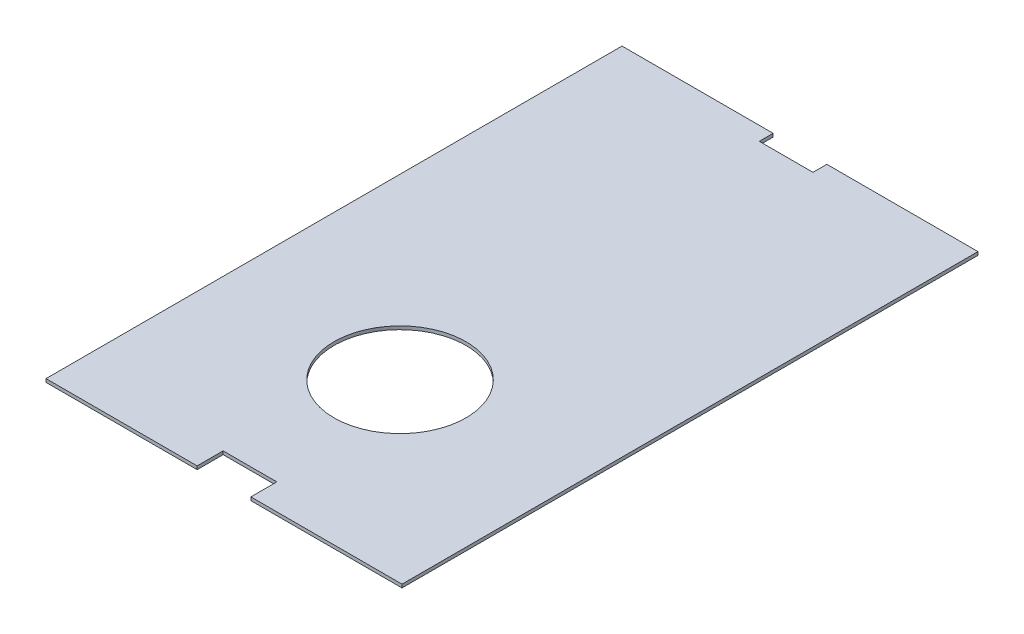
SolidWorks part; units mm, degrees
ref_plane "Front Plane" through (0, 0, 0) normal (0, 0, 1) x (1, 0, 0)
ref_plane "Top Plane" through (0, 0, 0) normal (0, 1, 0) x (1, 0, 0)
ref_plane "Right Plane" through (0, 0, 0) normal (1, 0, 0) x (0, 0, -1)
sketch "BaseSketch" plane through (0, 0, 0) normal (0, 1, 0) x (1, 0, 0)
  line L0 (0, -2.0955) -> (0, 2.0955) construction
  line L1 (-190.5, -317.5) -> (190.5, -317.5)
  line L2 (-190.5, -317.5) -> (-190.5, 317.5)
  line L3 (-190.5, 317.5) -> (190.5, 317.5)
  line L4 (190.5, -317.5) -> (190.5, 317.5)
  line L5 (-190.5, -317.5) -> (190.5, 317.5) construction
  line L6 (-190.5, 317.5) -> (190.5, -317.5) construction
  point P0 (0, 0)
  dimension "D1" = 90
extrude "Boss-Extrude1" add sketch "BaseSketch" along normal blind 3.81
sketch "Sketch7" plane through (0, 3.81, 0) normal (0, 1, 0) x (1, 0, 0)
  line L8 (205.5, -332.5) -> (205.5, 332.5)
  line L9 (205.5, 332.5) -> (-205.5, 332.5)
  line L10 (-205.5, 332.5) -> (-205.5, -332.5)
  line L11 (-205.5, -332.5) -> (205.5, -332.5)
  line L12 (205.5, -332.5) -> (205.5, 332.5)
  line L13 (205.5, 332.5) -> (-205.5, 332.5)
  line L14 (-205.5, 332.5) -> (-205.5, -332.5)
  line L15 (-205.5, -332.5) -> (205.5, -332.5)
  dimension "D1" = 15
extrude "Boss-Extrude2" add sketch "Sketch7" against normal up to surface (3.81 mm away) up to face at (0, 0, 0)
sketch "TabCutSketch" plane through (0, 3.81, 0) normal (0, 1, 0) x (1, 0, 0)
  line L1 (-31, -332.5) -> (31, -332.5)
  line L2 (-31, -332.5) -> (-31, -302.5)
  line L3 (-31, -302.5) -> (31, -302.5)
  line L4 (31, -332.5) -> (31, -302.5)
  line L5 (-205.5, -332.5) -> (205.5, -332.5) construction
  line L10 (0, 0) -> (0, 316.5) construction
  line L11 (0, 316.5) -> (0, 0) construction
  line L13 (31, 332.5) -> (-31, 332.5)
  line L14 (31, 332.5) -> (31, 316.5)
  line L15 (31, 316.5) -> (-31, 316.5)
  line L16 (-31, 332.5) -> (-31, 316.5)
  line L17 (0, 0) -> (0, -302.5) construction
  line L18 (205.5, 332.5) -> (-205.5, 332.5) construction
  point P0 (0, -332.5)
  dimension "D1" = 30
  dimension "D2" = 62
  dimension "D3" = 16
  dimension "D4" = 62
extrude "Cut-Extrude1" cut sketch "TabCutSketch" against normal through all
sketch "Sketch6" plane through (0, 3.81, 0) normal (0, 1, 0) x (1, 0, 0)
  line L0 (0, -129.3) -> (0, 316.5) construction
  line L1 (31, -332.5) -> (205.5, -332.5) construction
  line L2 (-31, 316.5) -> (31, 316.5) construction
  circle A0 centre (0, -129.3) radius 76.2
  dimension "D2" = 152.4
  dimension "D1" = 203.2
extrude "Cut-Extrude10" cut sketch "Sketch6" against normal blind 3.81
